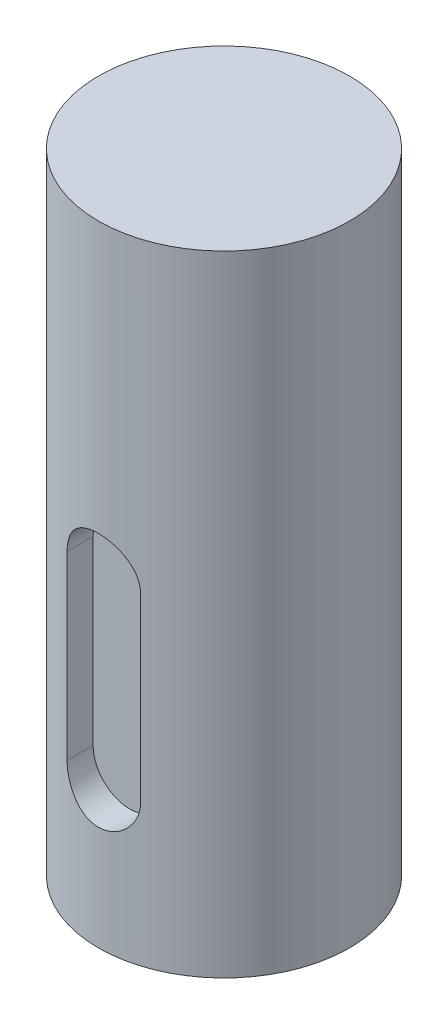
SolidWorks part; units mm, degrees
ref_plane "前视基准面" through (0, 0, 0) normal (0, 0, 1) x (1, 0, 0)
ref_plane "上视基准面" through (0, 0, 0) normal (0, 1, 0) x (1, 0, 0)
ref_plane "右视基准面" through (0, 0, 0) normal (1, 0, 0) x (0, 0, -1)
sketch "草图1" plane through (0, 0, 0) normal (0, 1, 0) x (1, 0, 0)
  circle A0 centre (0, 0) radius 19.9517
extrude "凸台-拉伸1" add sketch "草图1" along normal blind 100
ref_plane "基准面1" through (0, 0, 19.9517) normal (0, 0, 1) x (1, 0, 0)
sketch "草图2" plane through (0, 0, 19.9517) normal (0, 0, 1) x (1, 0, 0)
  line L0 (0, 22.4489) -> (0, 51.1979) construction
  line L1 (-5.8396, 22.4489) -> (-5.8396, 51.1979)
  line L2 (5.8396, 22.4489) -> (5.8396, 51.1979)
  arc A0 (-5.8396, 22.4489) -> (5.8396, 22.4489) centre (0, 22.4489) ccw
  arc A1 (5.8396, 51.1979) -> (-5.8396, 51.1979) centre (0, 51.1979) ccw
  point P3 (0, 36.8234)
extrude "切除-拉伸1" cut sketch "草图2" against normal blind 5
